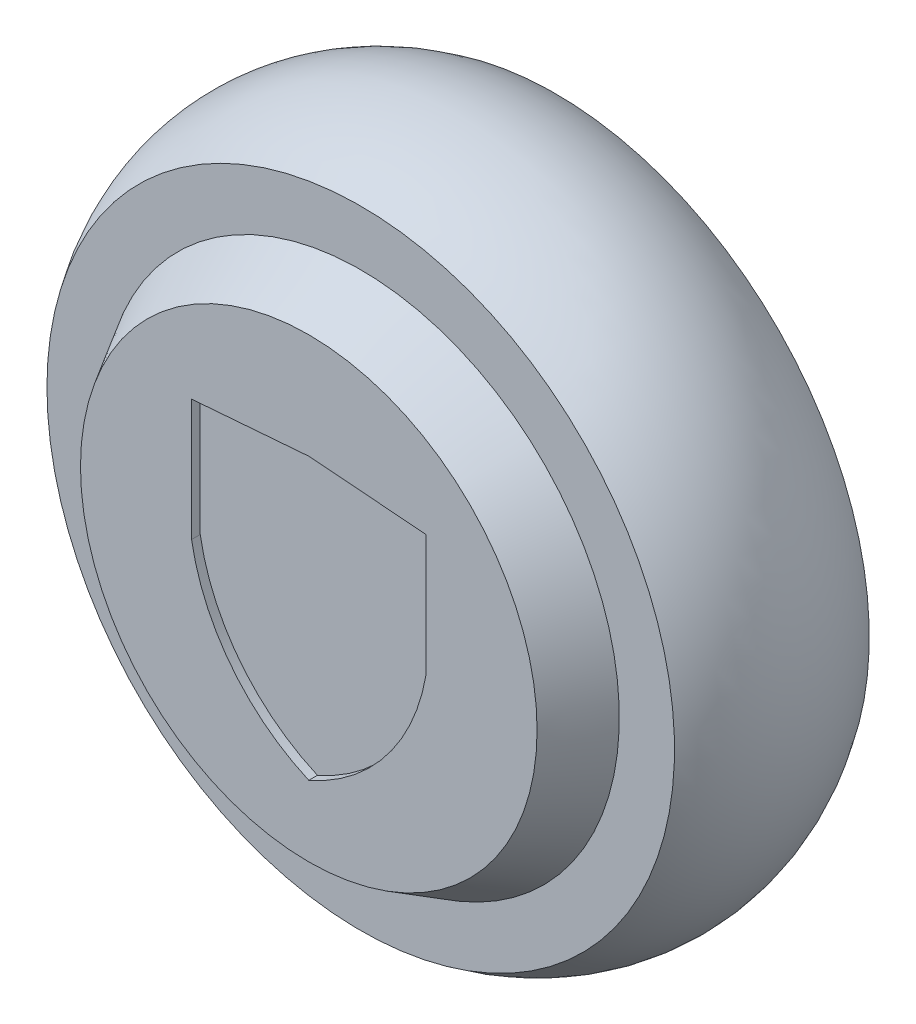
SolidWorks part; units mm, degrees
ref_plane "Спереди" through (0, 0, 0) normal (0, 0, 1) x (1, 0, 0)
ref_plane "Сверху" through (0, 0, 0) normal (0, 1, 0) x (1, 0, 0)
ref_plane "Справа" through (0, 0, 0) normal (1, 0, 0) x (0, 0, -1)
other "Configuration Table"
sketch "Эскиз1" plane through (0, 0, 0) normal (0, 0, 1) x (1, 0, 0)
  circle A0 centre (0, 0) radius 82.5
  dimension "D1" = 165
extrude "Бобышка-Вытянуть1" add sketch "Эскиз1" along normal blind 22.5 and the other way blind 22.5
sketch "Эскиз3" plane through (0, 0, 0) normal (1, 0, 0) x (0, 0, -1)
  line L0 (22.1108, 0) -> (-83.7864, 0) construction
  line L1 (-22.5, 0) -> (-22.5, 59.75)
  line L2 (-22.5, 82.5) -> (-22.5, -82.5) construction
  line L3 (-22.5, 59.75) -> (-34.5, 52.75)
  line L4 (-34.5, 52.75) -> (-34.5, 0)
  line L5 (-34.5, 0) -> (-22.5, 0)
  dimension "D1" = 52.75
  dimension "D2" = 59.75
  dimension "D3" = 12
revolve "Повернуть1" add sketch "Эскиз3" angle 360 about L0
sketch "Эскиз4" plane through (0, 0, -22.5) normal (0, 0, -1) x (-1, 0, 0)
  circle A0 centre (0, 0) radius 67.5
  dimension "D1" = 135
extrude "Вырез-Вытянуть1" cut sketch "Эскиз4" against normal blind 4
sketch "Эскиз5" plane through (0, 0, -18.5) normal (0, 0, -1) x (-1, 0, 0)
  circle A0 centre (0, 0) radius 52
  dimension "D1" = 104
extrude "Вырез-Вытянуть2" cut sketch "Эскиз5" against normal blind 48
sketch "Эскиз6" plane through (0, 0, -22.5) normal (0, 0, -1) x (-1, 0, 0)
  circle A0 centre (0, 0) radius 72.5
  dimension "D1" = 145
sketch "Эскиз7" plane through (0, 0, 0) normal (1, 0, 0) x (0, 0, -1)
  line L0 (22.5, -72.5) -> (22.5, 72.5) construction
  line L1 (22.5, -82.5) -> (22.5, 82.5) construction
  line L2 (-22.5, 82.5) -> (-22.5, -82.5) construction
  line L3 (-22.5, 72.5) -> (-31.9487, 72.5)
  line L4 (-31.9487, 72.5) -> (-31.9487, 102.6075)
  line L5 (-31.9487, 102.6075) -> (33.4899, 102.6075)
  line L6 (33.4899, 102.6075) -> (33.4899, 72.5)
  line L7 (33.4899, 72.5) -> (22.5, 72.5)
  line L8 (0, 0) -> (-22.5, 0) construction
  line L9 (-22.5, 59.75) -> (-22.5, -59.75) construction
  line L10 (0, 0) -> (0, 79.75) construction
  line L11 (22.5, 72.5) -> (-22.5, 72.5) construction
  arc A1 (22.5, 72.5) -> (-22.5, 72.5) centre (0, 41.2112) ccw
  point P21 (0, 79.75)
  dimension "D1" = 79.75
  dimension "D2" = 72.5
revolve "Вырез-Повернуть1" cut sketch "Эскиз7" angle 360 about L8
sketch "Эскиз8" plane through (0, 0, 34.5) normal (0, 0, 1) x (1, 0, 0)
  line L0 (0, 44.397) -> (0, -49.1004) construction
  line L1 (-27.08, 26.3184) -> (0, 28.434)
  line L2 (-27.08, 26.3184) -> (-27.08, -1.7816)
  line L3 (27.08, 26.3184) -> (0, 28.434)
  line L4 (27.08, 26.3184) -> (27.08, -1.7816)
  arc A0 (-27.08, -1.7816) -> (0, -36.4155) centre (18.5615, 6.0014) ccw
  arc A1 (27.08, -1.7816) -> (0, -36.4155) centre (-18.5615, 6.0014) cw
extrude "Вырез-Вытянуть3" cut sketch "Эскиз8" against normal blind 2
